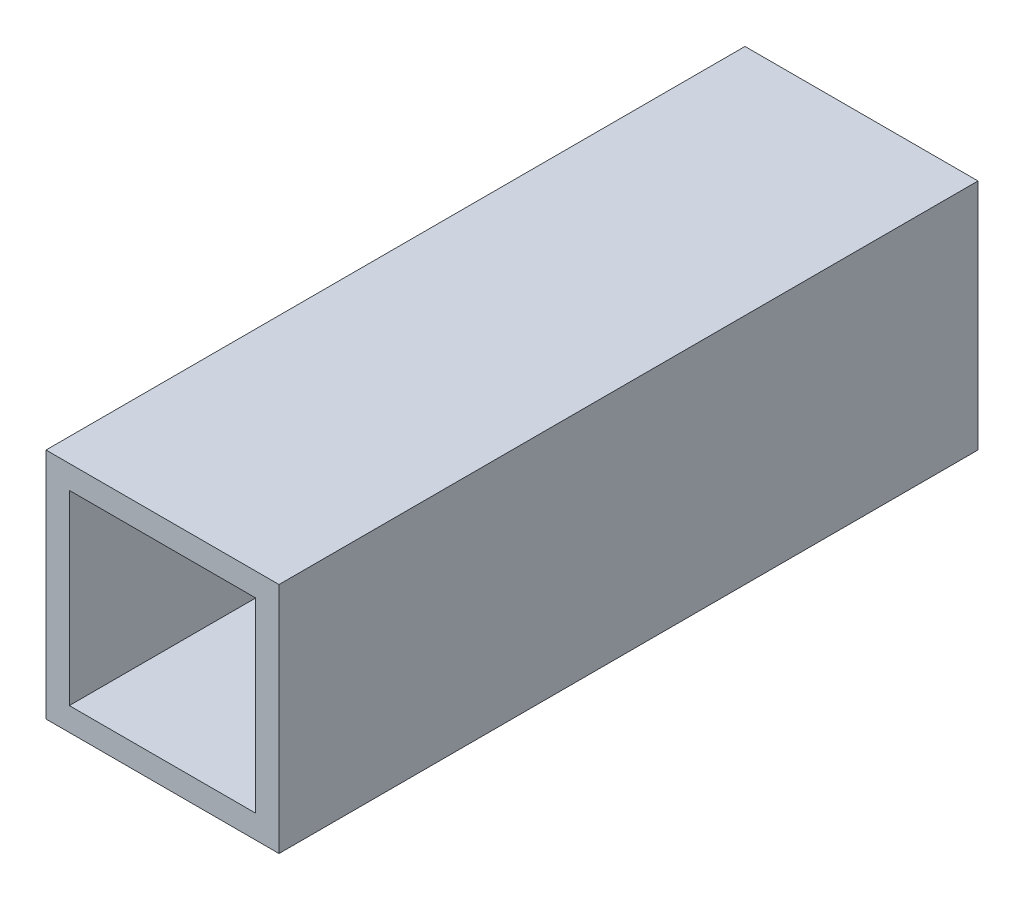
SolidWorks part; units mm, degrees
ref_plane "Front Plane" through (0, 0, 0) normal (0, 0, 1) x (1, 0, 0)
ref_plane "Top Plane" through (0, 0, 0) normal (0, 1, 0) x (1, 0, 0)
ref_plane "Right Plane" through (0, 0, 0) normal (1, 0, 0) x (0, 0, -1)
sketch "Sketch1" plane through (0, 0, 0) normal (0, 0, 1) x (1, 0, 0)
  line L0 (-20, 20) -> (-20, -20)
  line L1 (-25, 25) -> (25, 25)
  line L2 (-25, 25) -> (-25, -25)
  line L3 (-25, -25) -> (25, -25)
  line L4 (25, 25) -> (25, -25)
  line L5 (-20, -20) -> (20, -20)
  line L6 (20, 20) -> (20, -20)
  line L7 (-20, 20) -> (20, 20)
  dimension "tube_width" = 50
  dimension "D1" = 50
  dimension "D3" = 25
  dimension "D4" = 25
  dimension "tube_thickness" = 5
extrude "Boss-Extrude1" add sketch "Sketch1" along normal blind 150
sketch "Sketch2" plane through (0, 25, 0) normal (0, 1, 0) x (1, 0, 0)
  text T0 "<r180>z</r>" font "Century Gothic" height 40
ref_axis "Axis1" through (0, 0, -7.5) along (0, 0, 1)
equation "\"D1@Sketch1\"= \"tube_width@Sketch1\""
equation "\"D3@Sketch1\"=\"tube_width@Sketch1\"/2"
equation "\"D4@Sketch1\"=\"tube_width@Sketch1\"/2"
